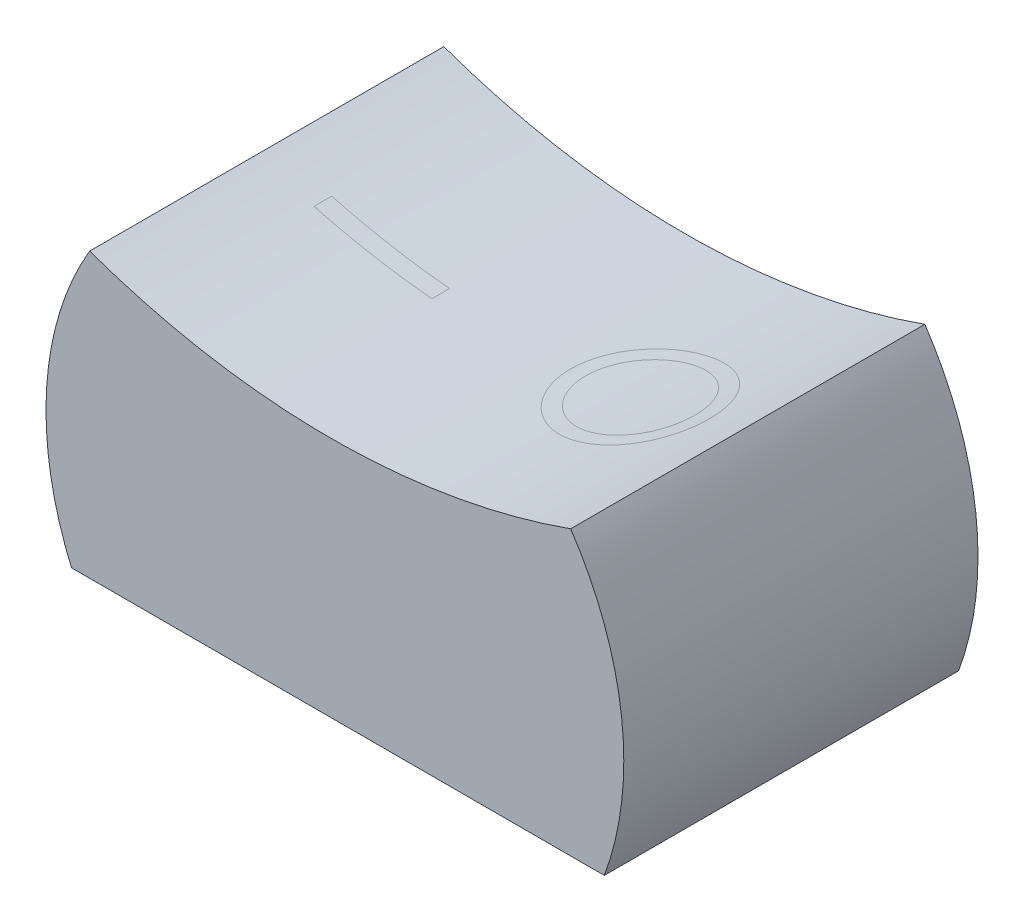
SolidWorks part; units mm, degrees
ref_plane "Ön Düzlem" through (0, 0, 0) normal (0, 0, 1) x (1, 0, 0)
ref_plane "Üst Düzlem" through (0, 0, 0) normal (0, 1, 0) x (1, 0, 0)
ref_plane "Sağ Düzlem" through (0, 0, 0) normal (1, 0, 0) x (0, 0, -1)
sketch "Çizim1" plane through (0, 0, 0) normal (0, 0, 1) x (1, 0, 0)
  line L1 (-7.8726, -1.2367) -> (0, -1.2367)
  line L4 (0, -3.3337) -> (0, 8.8426) construction
  line L7 (0, -1.2367) -> (7.1703, -1.2367)
  arc A2 (-7.3594, 6.7633) -> (-7.8726, -1.2367) centre (0.257, 2.2582) ccw
  arc A7 (6.2205, 6.7633) -> (7.1703, -1.2367) centre (-1.1287, 1.8343) cw
  arc A9 (-7.3594, 6.7633) -> (6.2205, 6.7633) centre (-0.5695, 25.8476) ccw
  dimension "D1" = 8
  dimension "D2" = 8
extrude "Yükseklik-Ekstrüzyon1" add sketch "Çizim1" along normal blind 10
sketch "Çizim3" plane through (0, 0, 0) normal (0, 0, -1) x (-1, 0, 0)
  circle A0 centre (0.5021, 1.8105) radius 0.925
ref_plane "Düzlem1" through (0, 0, -3.1632) normal (0, 0, 1) x (1, 0, 0)
sketch "Çizim4" plane through (0, 0, -3.1632) normal (0, 0, 1) x (1, 0, 0)
  circle A0 centre (-0.5021, 1.8105) radius 0.925
wrap "Sar3" sketch "Çizim4" wrap type scribe source sketch "Çizim4" face at (-0.459, 2.5142, 0)
ref_plane "Düzlem2" through (0, 7.0252, 0) normal (0, 1, 0) x (1, 0, 0)
sketch "Çizim5" plane through (0, 7.0252, 0) normal (0, 1, 0) x (1, 0, 0)
  line L0 (6.856, -5) -> (-11.6773, -5) construction
  line L3 (-2.4488, -4.7504) -> (-5.836, -4.7504)
  line L4 (-2.4488, -4.7504) -> (-2.4488, -5.2496)
  line L5 (-2.4488, -5.2496) -> (-5.836, -5.2496)
  line L6 (-5.836, -4.7504) -> (-5.836, -5.2496)
  line L7 (-2.4488, -4.7504) -> (-5.836, -5.2496) construction
  line L8 (-2.4488, -5.2496) -> (-5.836, -4.7504) construction
  line L11 (6.2205, -10) -> (6.2205, 0) construction
  line L12 (6.2205, -5) -> (-5.836, -5) construction
  circle A0 centre (3.2198, -5) radius 2
  circle A1 centre (3.2198, -5) radius 1.5742
  point P6 (-4.1424, -5)
  dimension "D1" = 4
wrap "Sar4" sketch "Çizim5" wrap type scribe source sketch "Çizim5" face at (-0.5695, 6.1773, 5)
shell "İç Boşaltma1" thickness 1 removed face at (-0.3512, -1.2367, 5)
